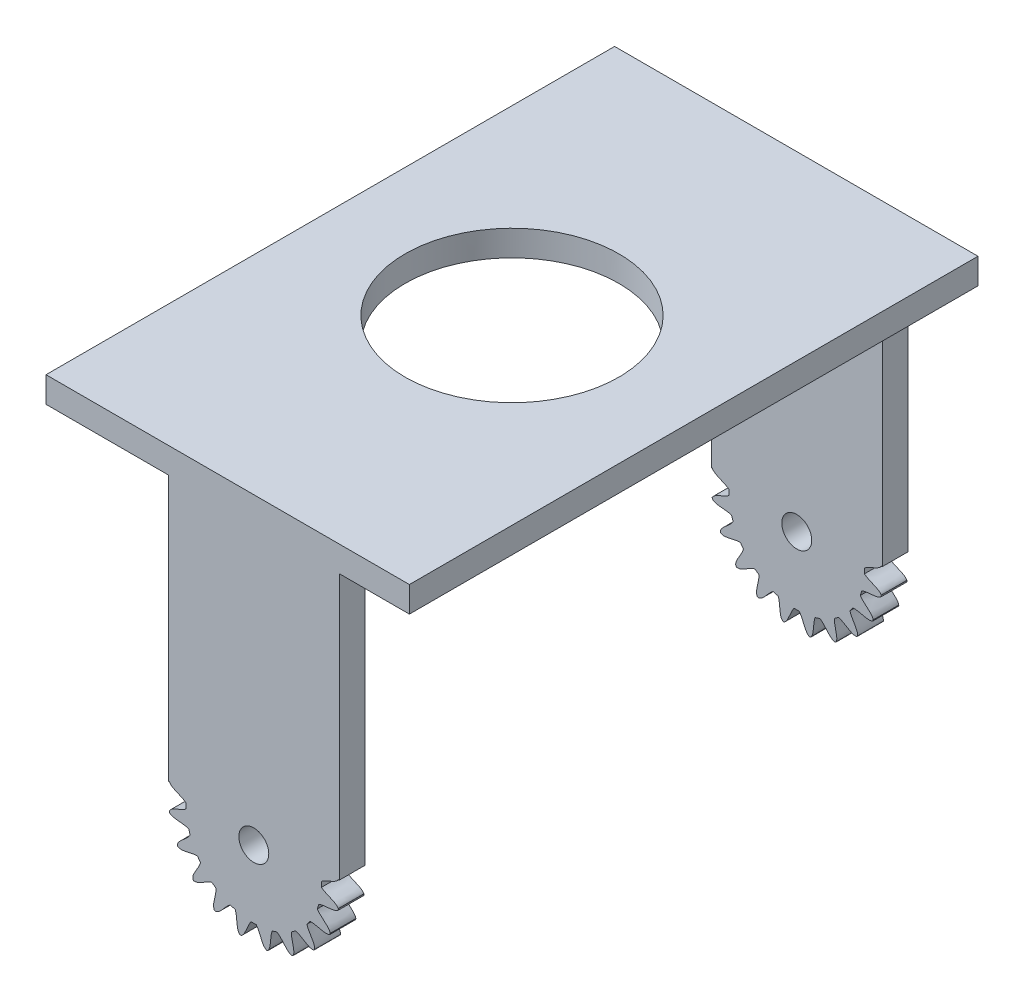
SolidWorks part; units mm, degrees
ref_plane "Plan de face" through (0, 0, 0) normal (0, 0, 1) x (1, 0, 0)
ref_plane "Plan de dessus" through (0, 0, 0) normal (0, 1, 0) x (1, 0, 0)
ref_plane "Plan de droite" through (0, 0, 0) normal (1, 0, 0) x (0, 0, -1)
sketch "Esquisse1" plane through (0, 0, 0) normal (0, 0, 1) x (1, 0, 0)
  line L1 (-13.8936, 26.5431) -> (26.1064, 26.5431)
  line L2 (-13.8936, 26.5431) -> (-13.8936, -38.4569)
  line L4 (26.1064, 26.5431) -> (26.1064, -38.4569)
  arc A1 (26.1064, -38.4569) -> (-13.8936, -38.4569) centre (6.1064, -38.4569) cw
  point P2 (24.7108, -35.0699)
  point P5 (-13.8936, -38.4569)
  point P7 (0, 0)
  point P8 (-14.3596, -35.1918)
  dimension "D1" = 40
  dimension "D2" = 65
extrude "Boss.-Extru.1" add sketch "Esquisse1" along normal blind 6
sketch "Esquisse2" plane through (0, 0, 6) normal (0, 0, 1) x (1, 0, 0)
  line L0 (6.1064, 26.5431) -> (6.1064, -15.994) construction
  line L1 (26.1064, 26.5431) -> (-13.8936, 26.5431) construction
  line L2 (26.1064, -38.4569) -> (26.1064, 26.5431) construction
  line L3 (-13.8936, 26.5431) -> (-13.8936, -38.4569) construction
  circle A0 centre (6.1064, -38.4569) radius 3.5
  arc A1 (-13.8936, -38.4569) -> (26.1064, -38.4569) centre (6.1064, -38.4569) ccw construction
  dimension "D1" = 7
extrude "Enlèv. mat.-Extru.1" cut sketch "Esquisse2" against normal blind 6
sketch "Esquisse3" plane through (0, 26.5431, 0) normal (0, 1, 0) x (1, 0, 0)
  line L1 (-42.5, 0) -> (42.5, 0)
  line L2 (-42.5, 0) -> (-42.5, -133)
  line L3 (-42.5, -133) -> (42.5, -133)
  line L4 (42.5, 0) -> (42.5, -133)
  line L5 (0, 6.6955) -> (0, -147.6284) construction
  dimension "D1" = 133
  dimension "D2" = 85
extrude "Boss.-Extru.2" add sketch "Esquisse3" along normal blind 6 contours L4 L3 L2 L1
ref_plane "Plan1" through (0, 0, 66.5) normal (0, 0, -1) x (-1, 0, 0)
mirror "Symétrie1" about plane through (0, 0, 66.5) normal (0, 0, -1) of "Enlèv. mat.-Extru.1", "Boss.-Extru.1"
ref_axis "Axe1" through (6.1064, -38.4569, 133) along (0, 0, -1)
sketch "Esquisse8" plane through (0, 0, 0) normal (0, 0, -1) x (-1, 0, 0)
  line L3 (-6.6779, -53.8349) -> (-5.4779, -53.8349) construction
  line L4 (-6.6779, -53.8349) -> (-7.7031, -52.5172) construction
  line L5 (-7.7031, -52.5172) -> (-8.0105, -50.3568) construction
  line L6 (-8.0105, -50.3568) -> (-9.0266, -49.9135) construction
  line L7 (-6.1064, -38.4569) -> (-6.1064, -65.0443) construction
  line L8 (-5.4779, -53.8349) -> (-4.4527, -52.5172) construction
  line L22 (-4.4527, -52.5172) -> (-4.1453, -50.3568) construction
  line L23 (-4.1453, -50.3568) -> (-3.1291, -49.9135) construction
  line L24 (-9.0266, -54.0562) -> (-1.723, -54.0562) construction
  line L25 (-5.4779, -54.2774) -> (-4.4527, -55.5952) construction
  line L26 (-4.4527, -55.5952) -> (-4.1453, -57.7556) construction
  line L27 (-4.1453, -57.7556) -> (-3.1291, -58.1989) construction
  line L28 (-6.6779, -54.2774) -> (-7.7031, -55.5952) construction
  line L29 (-7.7031, -55.5952) -> (-8.0105, -57.7556) construction
  line L30 (-8.0105, -57.7556) -> (-9.0266, -58.1989) construction
  line L31 (-6.6779, -54.2774) -> (-5.4779, -54.2774)
  arc A3 (-9.0266, -49.9135) -> (-3.1291, -49.9135) centre (-6.0779, -49.8349) cw construction
  arc A4 (-9.0266, -58.1989) -> (-3.1291, -58.1989) centre (-6.0779, -58.2774) ccw
  spline S0 degree 3 poles (-6.6779, -53.8349) (-7.7031, -52.5172) (-8.0105, -50.3568) (-9.0266, -49.9135) knots 0 0 0 0 1 1 1 1 construction
  spline S1 degree 3 poles (-5.4779, -53.8349) (-4.4527, -52.5172) (-4.1453, -50.3568) (-3.1291, -49.9135) knots 0 0 0 0 1 1 1 1 construction
  spline S2 degree 3 poles (-5.4779, -54.2774) (-4.4527, -55.5952) (-4.1453, -57.7556) (-3.1291, -58.1989) knots 0 0 0 0 1 1 1 1
  spline S3 degree 3 poles (-6.6779, -54.2774) (-7.7031, -55.5952) (-8.0105, -57.7556) (-9.0266, -58.1989) knots 0 0 0 0 1 1 1 1
  point P14 (-6.0779, -49.8349)
  point P25 (-6.0779, -58.2774)
  dimension "D1" = 1.2
  dimension "D2" = 3.9215
  dimension "D3" = 4
extrude "Enlèv. mat.-Extru.10" cut sketch "Esquisse8" against normal through all
pattern_circular "Répétition circulaire5" count 6 every 18 about axis through (6.1064, -38.4569, 0) along (0, 0, 1) of "Enlèv. mat.-Extru.10"
pattern_circular "Répétition circulaire7" count 6 every 18 about axis through (6.1064, -38.4569, 0) along (0, 0, 1) of "Enlèv. mat.-Extru.10" reverse direction yes
sketch "Esquisse9" plane through (0, 32.5431, 0) normal (0, 1, 0) x (1, 0, 0)
  line L0 (46.75, -66.5) -> (-46.75, -66.5) construction
  circle A0 centre (0, -66.5) radius 25
  dimension "D1" = 50
extrude "Enlèv. mat.-Extru.11" cut sketch "Esquisse9" against normal through all
